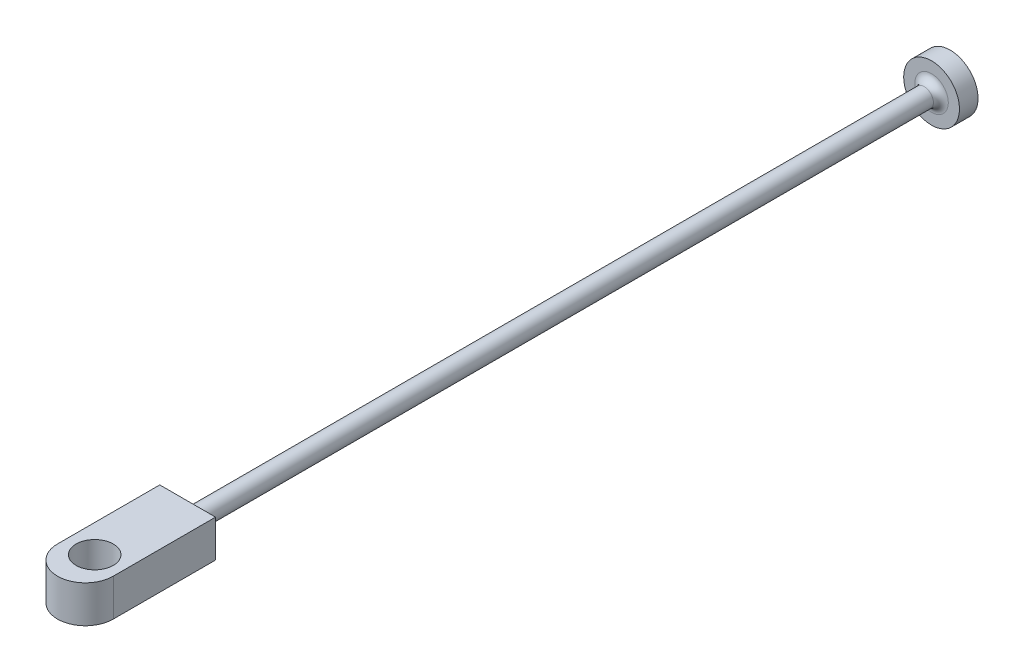
SolidWorks part; units mm, degrees
ref_plane "Front Plane" through (0, 0, 0) normal (0, 0, 1) x (1, 0, 0)
ref_plane "Top Plane" through (0, 0, 0) normal (0, 1, 0) x (1, 0, 0)
ref_plane "Right Plane" through (0, 0, 0) normal (1, 0, 0) x (0, 0, -1)
sketch "Sketch1" plane through (0, 0, 0) normal (0, 0, 1) x (1, 0, 0)
  circle A0 centre (50, 0) radius 2.5
extrude "Boss-Extrude1" add sketch "Sketch1" along normal blind 165 and the other way blind 35
sketch "Sketch2" plane through (0, 0, 165) normal (0, 0, 1) x (1, 0, 0)
  line L0 (50, 2.5) -> (50, 0) construction
  line L1 (42.5, 5) -> (57.5, 5)
  line L2 (42.5, 5) -> (42.5, -5)
  line L3 (42.5, -5) -> (57.5, -5)
  line L4 (57.5, 5) -> (57.5, -5)
  line L5 (42.5, 5) -> (57.5, -5) construction
  line L6 (42.5, -5) -> (57.5, 5) construction
  line L7 (50, 0) -> (52.5, 0) construction
  circle A0 centre (50, 0) radius 2.5 construction
  point P0 (50, 0)
  dimension "D1" = 15
  dimension "D2" = 10
extrude "Boss-Extrude2" add sketch "Sketch2" along normal blind 35
sketch "Sketch3" plane through (0, 5, 0) normal (0, 1, 0) x (1, 0, 0)
  line L0 (50, -200) -> (50, -190) construction
  line L1 (57.5, -200) -> (42.5, -200) construction
  line L2 (50, -190) -> (42.5, -190) construction
  line L3 (42.5, -200) -> (42.5, -165) construction
  circle A0 centre (50, -190) radius 5
  dimension "D1" = 10
  dimension "D2" = 10
extrude "Cut-Extrude1" cut sketch "Sketch3" against normal through all
fillet "Fillet1" 2 edges at (42.5, 0, 200) (57.5, 0, 200) type full round first side face at (42.5, 0, 182.5) second side face at (57.5, 0, 182.5) middle face at (50, 0, 200)
fillet "Fillet2" radius 2 1 edges at (52.5, 0, 165)
sketch "Sketch4" plane through (0, 0, -35) normal (0, 0, -1) x (-1, 0, 0)
  circle A0 centre (-50, 0) radius 7.5
  dimension "D1" = 15
extrude "Boss-Extrude3" add sketch "Sketch4" along normal blind 5
fillet "Fillet3" radius 2 1 edges at (52.5, 0, -35)
